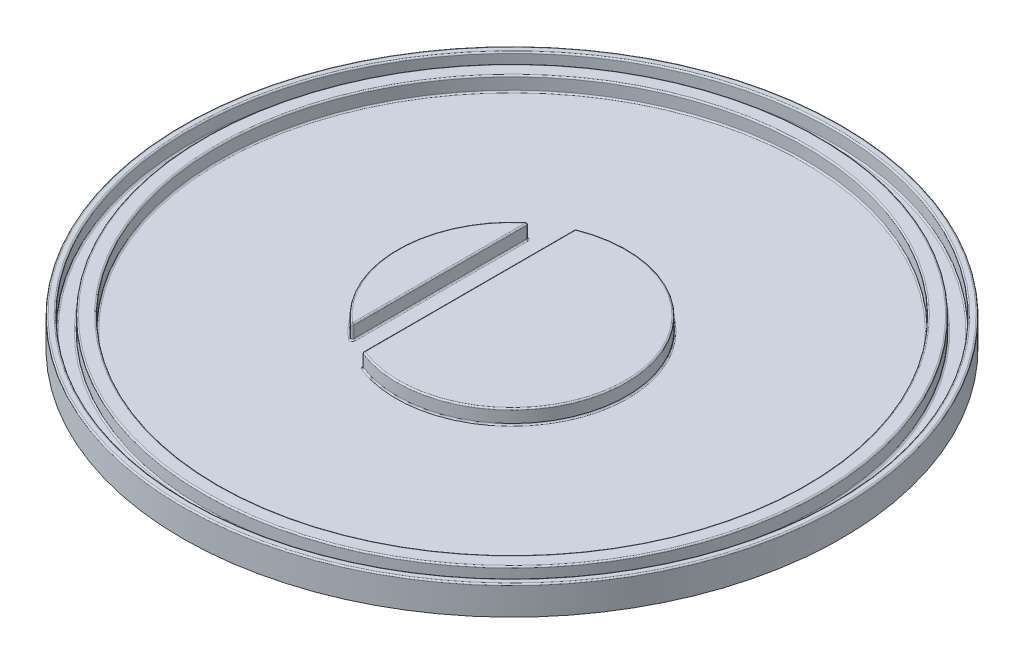
SolidWorks part; units mm, degrees
material "Silicon Rubber"
ref_plane "Front Plane" through (0, 0, 0) normal (0, 0, 1) x (1, 0, 0)
ref_plane "Top Plane" through (0, 0, 0) normal (0, 1, 0) x (1, 0, 0)
ref_plane "Right Plane" through (0, 0, 0) normal (1, 0, 0) x (0, 0, -1)
ref_axis "CentralAxis" through (0, 2.1, 0) along (0, -1, 0)
sketch "BaseS" plane through (0, 0, 0) normal (0, 1, 0) x (1, 0, 0)
  circle A0 centre (0, 0) radius 23
  dimension "Diameter" = 46
extrude "Base" add sketch "BaseS" along normal blind 1
sketch "OuterRingProfileS" plane through (0, 1, 0) normal (0, 1, 0) x (1, 0, 0)
  circle A0 centre (0, 0) radius 23 construction
  circle A1 centre (0, 0) radius 23
  circle A3 centre (0, 0) radius 22.5
  dimension "WallThickness" = 0.5
extrude "OuterRingProfile" add sketch "OuterRingProfileS" along normal blind 1
sketch "WireEncapsulatingS" plane through (0, 1, 0) normal (0, 1, 0) x (1, 0, 0)
  circle A0 centre (0, 0) radius 8
  circle A1 centre (0, 0) radius 20.5
  circle A2 centre (0, 0) radius 21.5
  circle A4 centre (0, 0) radius 22.5 construction
  dimension "InnerDiameter" = 16
  dimension "RefOuterDiameter1" = 43
  dimension "RefOuterDiameter2" = 41
  dimension "WallThickness" = 1
  dimension "OuterDiameterControl" = 1
extrude "WireEncapsulating" add sketch "WireEncapsulatingS" along normal blind 1 contours A0 | A2 A1 region at (0, 1, 0) region at (-20.8919, 1, 0)
sketch "WireAccessS" plane through (0, 2, 0) normal (0, 1, 0) x (1, 0, 0)
  line L0 (-5, 6.245) -> (-5, -6.245)
  line L1 (-3, 7.4162) -> (-3, -7.4162)
  line L2 (-5, 0) -> (-8, 0) construction
  circle A0 centre (0, 0) radius 8 construction
  arc A1 (-5, -6.245) -> (-3, -7.4162) centre (0, 0) ccw
  arc A2 (-3, 7.4162) -> (-5, 6.245) centre (0, 0) ccw
  dimension "CutoutWidth" = 2
  dimension "XDim" = 3
extrude "WireAccess" cut sketch "WireAccessS" against normal up to surface (1 mm away) up to face at (0, 1, 8)
fillet "WireEncapsulatingFillet" radius 0.1 19 edges at (0, 1, 20.5) (0, 2, 21.5) (0, 2, 20.5) (0, 1, 22.5) (0, 1, 21.5) (0, 2, 22.5) (0, 2, 23) (8, 1, 0) (-3, 1, 0) (-5, 1, 0) (-8, 1, 0) (-8, 2, 0) (-5, 2, 0) (8, 2, 0) (-3, 2, 0) (-3, 1.5, -7.4162) (-3, 1.5, 7.4162) (-5, 1.5, 6.245) (-5, 1.5, -6.245)
